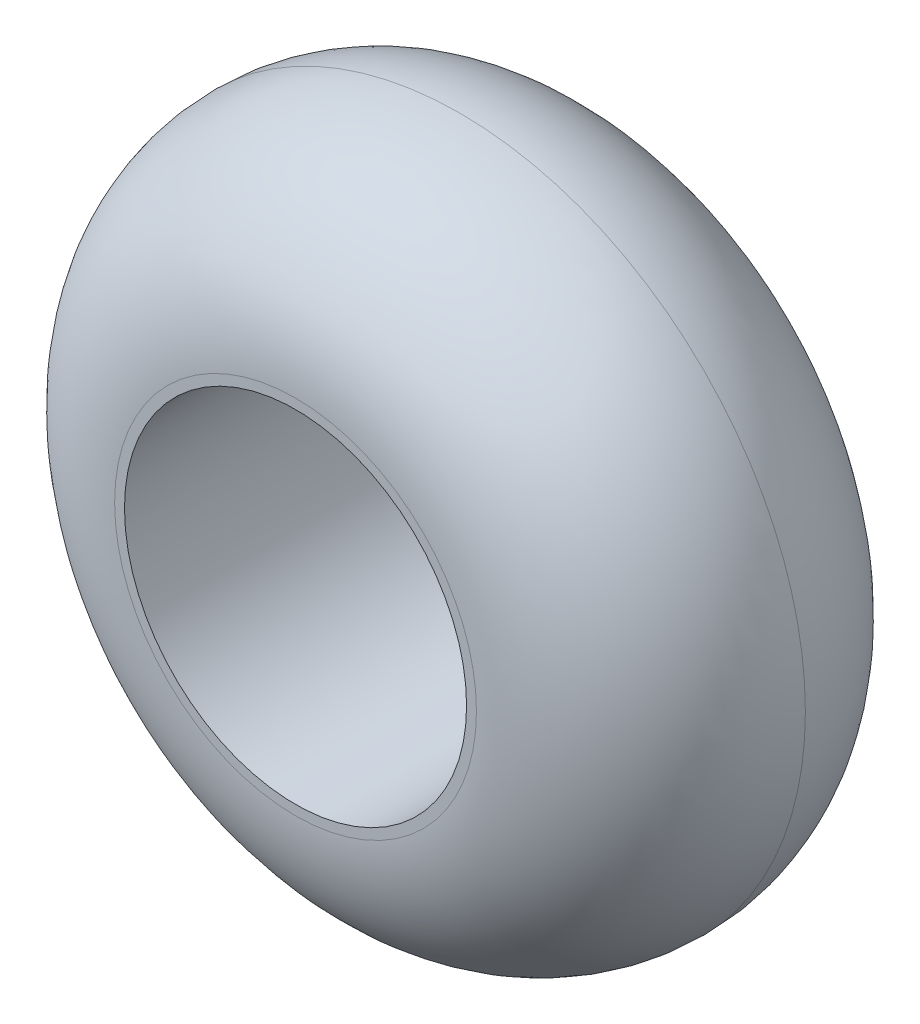
SolidWorks part; units mm, degrees
ref_plane "Plan de face" through (0, 0, 0) normal (0, 0, 1) x (1, 0, 0)
ref_plane "Plan de dessus" through (0, 0, 0) normal (0, 1, 0) x (1, 0, 0)
ref_plane "Plan de droite" through (0, 0, 0) normal (1, 0, 0) x (0, 0, -1)
sketch "Esquisse1" plane through (0, 0, 0) normal (0, 0, 1) x (1, 0, 0)
  circle A0 centre (0, 0) radius 2.6
  circle A1 centre (0, 0) radius 5.25
  dimension "D1" = 5.2
  dimension "D2" = 10.5
extrude "Boss.-Extru.1" add sketch "Esquisse1" along normal blind 5
fillet "Congé1" radius 2.5 2 edges at (5.25, 0, 0) (5.25, 0, 5)
